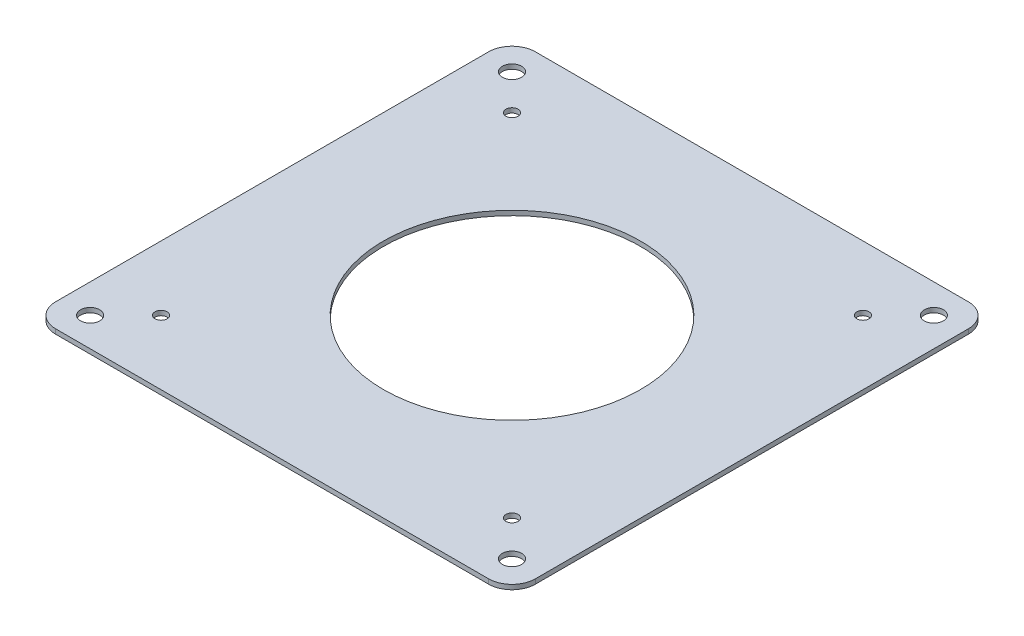
SolidWorks part; units mm, degrees
ref_plane "Front Plane" through (0, 0, 0) normal (0, 0, 1) x (1, 0, 0)
ref_plane "Top Plane" through (0, 0, 0) normal (0, 1, 0) x (1, 0, 0)
ref_plane "Right Plane" through (0, 0, 0) normal (1, 0, 0) x (0, 0, -1)
sketch "Sketch1" plane through (0, 0, 0) normal (0, 1, 0) x (1, 0, 0)
  line L1 (-46.2, -51.2) -> (46.2, -51.2)
  line L2 (-51.2, -46.2) -> (-51.2, 46.2)
  line L3 (-46.2, 51.2) -> (46.2, 51.2)
  line L4 (51.2, -46.2) -> (51.2, 46.2)
  line L5 (-51.2, -51.2) -> (51.2, 51.2) construction
  line L6 (-51.2, 51.2) -> (51.2, -51.2) construction
  arc A0 (46.2, -51.2) -> (51.2, -46.2) centre (46.2, -46.2) ccw
  arc A1 (-46.2, -51.2) -> (-51.2, -46.2) centre (-46.2, -46.2) cw
  arc A2 (-51.2, 46.2) -> (-46.2, 51.2) centre (-46.2, 46.2) cw
  arc A3 (46.2, 51.2) -> (51.2, 46.2) centre (46.2, 46.2) cw
  point P0 (0, 0)
  dimension "D3" = 5
  dimension "D1" = 102.4
  dimension "D2" = 102.4
sketch "Sketch7" plane through (0, 0, 0) normal (0, 0, 1) x (1, 0, 0)
  line L0 (0, 0) -> (0, 37.9069) construction
base flange "Base-Flange1" sketch "Sketch1" thickness 1 reverse thickness direction no parameters "D1"=1
sketch "Sketch6" plane through (0, 0, 0) normal (0, 1, 0) x (1, 0, 0)
  circle A0 centre (0, 0) radius 27.45
  dimension "D1" = 54.9
extrude "Cut-Extrude1" cut sketch "Sketch6" against normal blind 10 contours A0 normal cut yes
sketch "Sketch8" plane through (0, 0, 0) normal (0, 1, 0) x (1, 0, 0)
  line L0 (51.2, -46.2) -> (51.2, 46.2) construction
  line L1 (46.2, 51.2) -> (-46.2, 51.2) construction
  circle A0 centre (45.02, 45.02) radius 2.05
  circle A1 centre (37.45, 37.45) radius 1.3
  dimension "D5" = 4.1
  dimension "D6" = 2.6
  dimension "D1" = 6.18
  dimension "D2" = 6.18
  dimension "D3" = 13.75
  dimension "D4" = 13.75
extrude "Cut-Extrude3" cut sketch "Sketch8" against normal blind 10 normal cut yes
pattern_circular "CirPattern2" count 4 over 360 about axis through (0, 0, 0) along (0, 1, 0) of "Cut-Extrude3"
sketch "Bend-Lines1" plane through (0, 0, 0) normal (0, 1, 0) x (1, 0, 0)
sketch "Bounding-Box1" plane through (0, 0, 0) normal (0, 1, 0) x (1, 0, 0)
sheet metal parameters "Sheet-Metal(1)" thickness 1 parameters "D1"=1
flat pattern "Flat-Pattern(1)" [suppressed]
sketch "Bend-Lines2" plane through (0, 0, 0) normal (0, 1, 0) x (1, 0, 0)
sketch "Bounding-Box2" [suppressed] plane through (0, 0, 0) normal (0, 1, 0) x (1, 0, 0)
sheet metal parameters "Sheet-Metal(6)" thickness 1 parameters "D1"=1
flat pattern "Flat-Pattern(1)"
sketch "Bend-Lines2" plane through (0, 0, 0) normal (0, 1, 0) x (1, 0, 0)
sketch "Bounding-Box2" [suppressed] plane through (0, 0, 0) normal (0, 1, 0) x (1, 0, 0)
sheet metal parameters "Sheet-Metal(11)" thickness 1 parameters "D1"=1
flat pattern "Flat-Pattern(1)"
sketch "Bend-Lines2" plane through (0, 0, 0) normal (0, 1, 0) x (1, 0, 0)
sketch "Bounding-Box2" [suppressed] plane through (0, 0, 0) normal (0, 1, 0) x (1, 0, 0)
sheet metal parameters "Sheet-Metal(12)" thickness 1 parameters "D1"=1
flat pattern "Flat-Pattern(1)"
sketch "Bend-Lines2" plane through (0, 0, 0) normal (0, 1, 0) x (1, 0, 0)
sketch "Bounding-Box2" [suppressed] plane through (0, 0, 0) normal (0, 1, 0) x (1, 0, 0)
